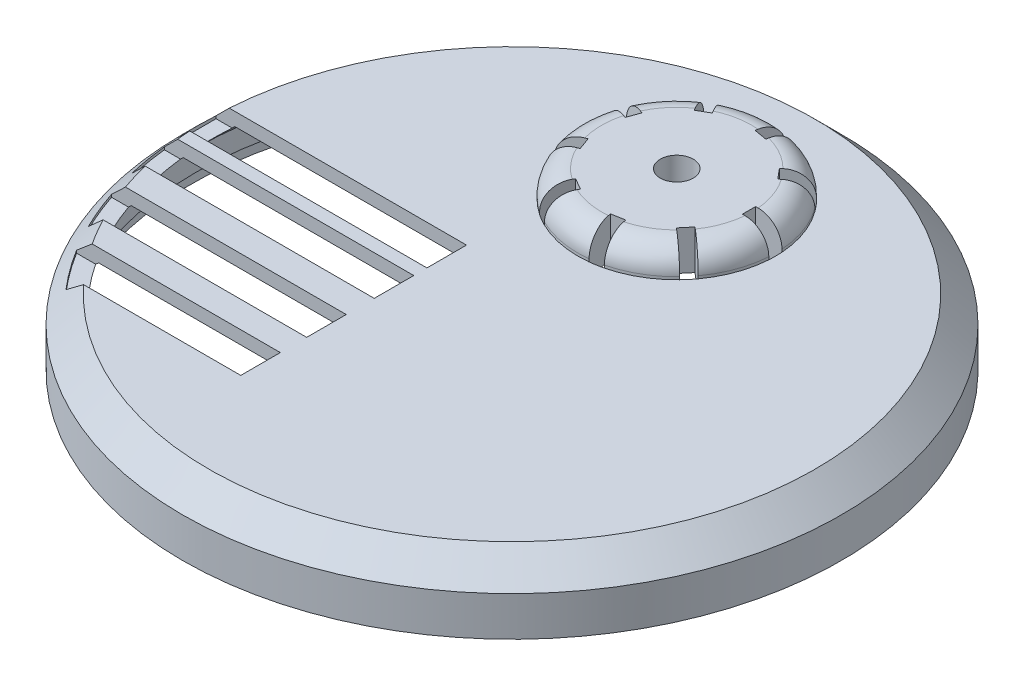
SolidWorks part; units mm, degrees
ref_plane "Front Plane" through (0, 0, 0) normal (0, 0, 1) x (1, 0, 0)
ref_plane "Top Plane" through (0, 0, 0) normal (0, 1, 0) x (1, 0, 0)
ref_plane "Right Plane" through (0, 0, 0) normal (1, 0, 0) x (0, 0, -1)
sketch "Sketch1" plane through (0, 0, 0) normal (0, 1, 0) x (1, 0, 0)
  circle A0 centre (0, 0) radius 31.75
  dimension "D1" = 63.5
extrude "Boss-Extrude1" add sketch "Sketch1" along normal blind 6.35
chamfer "Chamfer2" distance 2.54 angle 45 1 edges at (0, 6.35, 31.75)
sketch "Sketch2" plane through (0, 6.35, 0) normal (0, 1, 0) x (1, 0, 0)
  line L0 (0, 0) -> (0, 37.1387) construction
  line L1 (0, 0) -> (-38.6212, 0) construction
  circle A0 centre (0, 15.875) radius 1.5875
  circle A1 centre (0, 15.875) radius 9.525
  dimension "D1" = 15.875
  dimension "D2" = 19.05
  dimension "D3" = 3.175
extrude "Boss-Extrude2" add sketch "Sketch2" along normal blind 2.54
extrude "Cut-Extrude1" cut sketch "Sketch2<2>" against normal through all contours A0 region at (0, 6.35, -15.875)
sketch "Sketch2<2>" plane through (0, 6.35, 0) normal (0, 1, 0) x (1, 0, 0) same geometry as "Sketch2"
fillet "Fillet1" radius 2.286 1 edges at (0, 8.89, -6.35)
sketch "Sketch4" plane through (0, 8.89, 0) normal (0, 1, 0) x (1, 0, 0)
  line L0 (0, 15.875) -> (19.9948, 15.875) construction
  line L1 (9.5038, 16.51) -> (6.9638, 16.51)
  line L2 (6.9638, 16.51) -> (6.9638, 15.24)
  line L3 (6.9638, 15.24) -> (9.5038, 15.24)
  arc A0 (9.5038, 16.51) -> (9.5038, 15.24) centre (0, 15.875) cw
  circle A2 centre (0, 15.875) radius 9.525 construction
  dimension "D1" = 1.27
  dimension "D2" = 2.54
extrude "Cut-Extrude4" cut sketch "Sketch4" against normal through all
pattern_circular "CirPattern1" count 9 over 360 about axis through (0, 8.89, -15.875) along (0, 1, 0) of "Cut-Extrude4"
sketch "Sketch5" plane through (0, 6.35, 0) normal (0, 1, 0) x (1, 0, 0)
  line L0 (-37.7849, 0) -> (10.6436, 0) construction
  line L1 (-6.2904, -2.54) -> (-38.9139, -2.54) construction
  line L2 (-30.4204, -1.905) -> (-6.2904, -1.905)
  line L3 (-30.4204, -1.905) -> (-30.4204, 1.905)
  line L4 (-30.4204, 1.905) -> (-6.2904, 1.905)
  line L5 (-6.2904, -1.905) -> (-6.2904, 1.905)
  line L6 (-6.2904, -3.175) -> (-6.2904, -6.985)
  line L7 (-30.3193, -3.175) -> (-6.2904, -3.175)
  line L8 (-29.6688, -6.985) -> (-6.2904, -6.985)
  line L9 (-6.2904, -8.3342) -> (-40.8552, -8.3342) construction
  line L10 (-6.2904, -13.4934) -> (-6.2904, -9.6834)
  line L11 (-27.3306, -13.4934) -> (-6.2904, -13.4934)
  line L12 (-28.9009, -9.6834) -> (-6.2904, -9.6834)
  line L13 (-6.2904, -14.7634) -> (-38.9139, -14.7634) construction
  line L14 (-6.2904, -16.0334) -> (-6.2904, -19.8434)
  line L15 (-25.9222, -16.0334) -> (-6.2904, -16.0334)
  line L16 (-23.1359, -19.8434) -> (-6.2904, -19.8434)
  circle A0 centre (0, 0) radius 30.48 construction
  circle A1 centre (0, 15.875) radius 1.5875 construction
  arc A2 (-30.3193, -3.175) -> (-29.6688, -6.985) centre (0.6285, 0.148) ccw
  arc A3 (-28.9009, -9.6834) -> (-27.3306, -13.4934) centre (0, 0) ccw
  arc A4 (-25.9222, -16.0334) -> (-23.1359, -19.8434) centre (0, 0) ccw
  point P15 (0, 0)
  dimension "D1" = 60.96
  dimension "D2" = 15.875
  dimension "D3" = 3.81
  dimension "D4" = 24.13
  dimension "D5" = 0.635
  dimension "D6" = 5.1592
  dimension "D7" = 5.08
extrude "Cut-Extrude5" cut sketch "Sketch5" against normal blind 1.524
sketch "Sketch6" plane through (0, 0, 0) normal (1, 0, 0) x (0, 0, -1)
  line L0 (-30.48, 3.2839) -> (-28.6839, 5.08)
  line L14 (-30.48, 3.2839) -> (-30.48, 1.27)
  line L16 (-30.48, 1.27) -> (-30.9902, 1.27)
  line L17 (-30.9902, 1.27) -> (-30.9902, -0.5611)
  line L18 (0, 0) -> (0, -8.8569) construction
  line L27 (0, -0.5611) -> (0, 5.08)
  line L28 (-28.6839, 5.08) -> (0, 5.08)
  line L32 (-30.9902, -0.5611) -> (0, -0.5611)
revolve "Cut-Revolve1" cut sketch "Sketch6" angle 360 about L18
